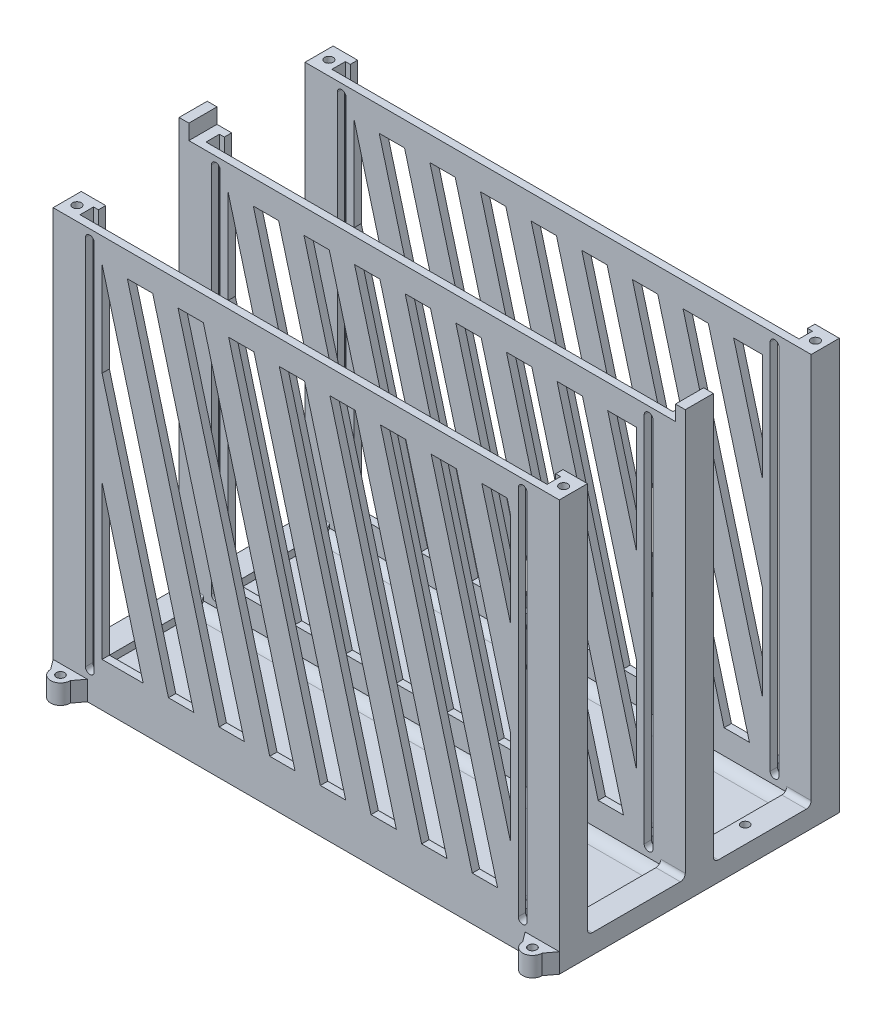
SolidWorks part; units mm, degrees
ref_plane "Front Plane" through (0, 0, 0) normal (0, 0, 1) x (1, 0, 0)
ref_plane "Top Plane" through (0, 0, 0) normal (0, 1, 0) x (1, 0, 0)
ref_plane "Right Plane" through (0, 0, 0) normal (1, 0, 0) x (0, 0, -1)
sketch "Sketch1" plane through (0, 0, 0) normal (0, 1, 0) x (1, 0, 0)
  line L0 (-95.5, 0) -> (95.5, 0) construction
  line L5 (-95.5, 2.75) -> (-93.5, 2.75)
  line L6 (-95.5, -2.75) -> (-95.5, 2.75)
  line L7 (-93.5, 2.75) -> (-93.5, 5.75)
  line L8 (-93.5, 5.75) -> (-103.5, 5.75)
  line L9 (-103.5, 5.75) -> (-103.5, -5.75)
  line L10 (-103.5, -5.75) -> (-93.5, -5.75)
  line L11 (-93.5, -5.75) -> (-93.5, -2.75)
  line L12 (-93.5, -2.75) -> (-95.5, -2.75)
  line L13 (-93.5, -2.75) -> (-93.5, -36.1204) construction
  line L14 (0, -55) -> (0, 55) construction
  line L15 (93.5, -5.75) -> (93.5, -2.75)
  line L16 (103.5, -5.75) -> (93.5, -5.75)
  line L17 (103.5, 5.75) -> (103.5, -5.75)
  line L18 (93.5, 5.75) -> (103.5, 5.75)
  line L19 (93.5, 2.75) -> (93.5, 5.75)
  line L20 (95.5, 2.75) -> (93.5, 2.75)
  line L21 (95.5, -2.75) -> (95.5, 2.75)
  line L22 (93.5, -2.75) -> (95.5, -2.75)
  line L23 (-93.5, 5.75) -> (93.5, 5.75)
  line L24 (-93.5, -5.75) -> (93.5, -5.75)
  line L25 (-93.5, -2.75) -> (93.5, -2.75)
  line L26 (93.5, 2.75) -> (-93.5, 2.75)
  line L27 (-93.5, -54.25) -> (-95.5, -54.25)
  line L28 (-95.5, -54.25) -> (-95.5, -48.75)
  line L29 (-95.5, -48.75) -> (-93.5, -48.75)
  line L30 (-93.5, -48.75) -> (-93.5, -45.75)
  line L31 (-93.5, -45.75) -> (-103.5, -45.75)
  line L32 (-103.5, -45.75) -> (-103.5, -57.25)
  line L33 (-103.5, -57.25) -> (-93.5, -57.25)
  line L34 (-93.5, -57.25) -> (-93.5, -54.25)
  line L35 (93.5, -57.25) -> (93.5, -54.25)
  line L36 (93.5, -54.25) -> (95.5, -54.25)
  line L37 (95.5, -54.25) -> (95.5, -48.75)
  line L38 (95.5, -48.75) -> (93.5, -48.75)
  line L39 (93.5, -48.75) -> (93.5, -45.75)
  line L40 (93.5, -45.75) -> (103.5, -45.75)
  line L41 (103.5, -45.75) -> (103.5, -57.25)
  line L42 (103.5, -57.25) -> (93.5, -57.25)
  line L43 (-93.5, -45.75) -> (93.5, -45.75)
  line L44 (93.5, -48.75) -> (-93.5, -48.75)
  line L45 (-93.5, -54.25) -> (93.5, -54.25)
  line L46 (-93.5, -57.25) -> (93.5, -57.25)
  line L47 (-93.5, -105.75) -> (-95.5, -105.75)
  line L48 (-95.5, -105.75) -> (-95.5, -100.25)
  line L49 (-95.5, -100.25) -> (-93.5, -100.25)
  line L50 (-93.5, -100.25) -> (-93.5, -97.25)
  line L51 (-93.5, -97.25) -> (-103.5, -97.25)
  line L52 (-103.5, -97.25) -> (-103.5, -108.75)
  line L53 (-103.5, -108.75) -> (-93.5, -108.75)
  line L54 (-93.5, -108.75) -> (-93.5, -105.75)
  line L55 (93.5, -108.75) -> (93.5, -105.75)
  line L56 (93.5, -105.75) -> (95.5, -105.75)
  line L57 (95.5, -105.75) -> (95.5, -100.25)
  line L58 (95.5, -100.25) -> (93.5, -100.25)
  line L59 (93.5, -100.25) -> (93.5, -97.25)
  line L60 (93.5, -97.25) -> (103.5, -97.25)
  line L61 (103.5, -97.25) -> (103.5, -108.75)
  line L62 (103.5, -108.75) -> (93.5, -108.75)
  line L63 (-93.5, -97.25) -> (93.5, -97.25)
  line L64 (93.5, -100.25) -> (-93.5, -100.25)
  line L65 (-93.5, -105.75) -> (93.5, -105.75)
  line L66 (-93.5, -108.75) -> (93.5, -108.75)
  line L67 (-103.5, -5.75) -> (-103.5, -45.75)
  line L68 (-93.5, -5.75) -> (-93.5, -45.75)
  line L69 (93.5, -5.75) -> (93.5, -45.75)
  line L70 (103.5, -5.75) -> (103.5, -45.75)
  line L71 (103.5, -57.25) -> (103.5, -97.25)
  line L72 (93.5, -97.25) -> (93.5, -57.25)
  line L73 (-103.5, -97.25) -> (-103.5, -57.25)
  line L74 (-93.5, -97.25) -> (-93.5, -57.25)
  line L75 (0, 5.75) -> (0, 9.75) construction
  line L76 (-96.5, 9.75) -> (96.5, 9.75) construction
  line L77 (-100.5, 9.75) -> (-103.5, 5.75)
  line L78 (-96.5, 8.05) -> (-96.5, 5.75) construction
  line L79 (-92.5, 9.75) -> (-89.5, 5.75)
  line L80 (92.5, 9.75) -> (89.5, 5.75)
  line L81 (100.5, 9.75) -> (103.5, 5.75)
  line L82 (-103.5, -51.5) -> (103.5, -51.5) construction
  line L83 (100.5, -112.75) -> (103.5, -108.75)
  line L84 (92.5, -112.75) -> (89.5, -108.75)
  line L85 (-92.5, -112.75) -> (-89.5, -108.75)
  line L86 (-100.5, -112.75) -> (-103.5, -108.75)
  circle A1 centre (96.5, 9.75) radius 1.7
  circle A2 centre (-96.5, 9.75) radius 1.7
  circle A4 centre (-96.5, 9.75) radius 4
  circle A5 centre (96.5, 9.75) radius 4
  circle A7 centre (96.5, 9.75) radius 1.7
  circle A8 centre (96.5, -112.75) radius 1.7
  circle A9 centre (96.5, -112.75) radius 4
  circle A10 centre (-96.5, -112.75) radius 1.7
  circle A12 centre (-96.5, -112.75) radius 4
  point P3 (0, 0)
  point P6 (95.5, 0)
  point P9 (-95.5, 0)
  point P61 (0, 9.75)
  dimension "D11" = 3.4
  dimension "D12" = 4
  dimension "D1" = 191
  dimension "D2" = 5.5
  dimension "D3" = 2
  dimension "D4" = 3
  dimension "D5" = 3
  dimension "D6" = 2
  dimension "D7" = 10
  dimension "D8" = 193
  dimension "D10" = 40
  dimension "D9" = 3
extrude "Boss-Extrude1" add sketch "Sketch1" against normal blind 3.2 contours L53 L54 L47 L48 L49 L50 L51 L52 | L54 L66 L55 L65 | L64 L59 L63 L50 | L34 L46 L35 L45 | L33 L34 L27 L28 L29 L30 L31 L32 | L44 L39 L43 L30 | L25 L11 L24 L15 | L26 L19 L23 L7 | L22 L15 L16 L17 L18 L19 L20 L21 | L42 L41 L40 L39 L38 L37 L36 L35 | L62 L61 L60 L59 L58 L57 L56 L55 | L11 L12 L6 L5 L7 L8 L9 L10 | L51 L74 L33 L73 | L68 L10 L67 L31 | L72 L60 L71 L42 | L70 L16 L69 L40 region at (-98.9231, 0, 0) region at (0, 0, -4.25) region at (98.9231, 0, 0) region at (0, 0, 4.25) region at (-98.5, 0, 25.75) region at (98.5, 0, 25.75) region at (0, 0, 47.25) region at (-98.9231, 0, 51.5) region at (98.9231, 0, 51.5) region at (-98.5, 0, 77.25) region at (0, 0, 55.75) region at (-98.9231, 0, 103) region at (98.5, 0, 77.25) region at (0, 0, 98.75) region at (98.9231, 0, 103) region at (0, 0, 107.25)
extrude "Boss-Extrude2" add sketch "Sketch1<4>" along normal blind 160 contours L53 L54 L47 L48 L49 L50 L51 L52 | L33 L34 L27 L28 L29 L30 L31 L32 | L11 L12 L6 L5 L7 L8 L9 L10 | L62 L61 L60 L59 L58 L57 L56 L55 | L42 L41 L40 L39 L38 L37 L36 L35 | L22 L15 L16 L17 L18 L19 L20 L21 region at (-98.9231, 0, 0) region at (98.9231, 0, 0) region at (-98.9231, 0, 51.5) region at (98.9231, 0, 51.5) region at (-98.9231, 0, 103) region at (98.9231, 0, 103)
sketch "Sketch1<4>" plane through (0, 0, 0) normal (0, 1, 0) x (1, 0, 0) same geometry as "Sketch1"
extrude "Boss-Extrude3" add sketch "Sketch1<5>" against normal blind 5 from offset 3 contours L53 L54 L47 L48 L49 L50 L51 L52 | L54 L66 L55 L65 | L47 L65 L56 L57 L58 L64 L49 L48 | L64 L59 L63 L50 | L51 L74 L33 L73 | L33 L34 L27 L28 L29 L30 L31 L32 | L34 L46 L35 L45 | L44 L39 L43 L30 | L68 L10 L67 L31 | L11 L12 L6 L5 L7 L8 L9 L10 | L25 L11 L24 L15 | L26 L19 L23 L7 | L22 L15 L16 L17 L18 L19 L20 L21 | L70 L16 L69 L40 | L42 L41 L40 L39 L38 L37 L36 L35 | L72 L60 L71 L42 | L62 L61 L60 L59 L58 L57 L56 L55 | L27 L45 L36 L37 L38 L44 L29 L28 | L20 L26 L5 L6 L12 L25 L22 L21 | L74 L63 L72 L46 | L69 L24 L68 L43 region at (-98.9231, 0, 0) region at (0, 0, 0) region at (0, 0, -4.25) region at (98.9231, 0, 0) region at (0, 0, 4.25) region at (-98.5, 0, 25.75) region at (0, 0, 25.75) region at (98.5, 0, 25.75) region at (0, 0, 47.25) region at (-98.9231, 0, 51.5) region at (98.9231, 0, 51.5) region at (0, 0, 51.5) region at (-98.5, 0, 77.25) region at (0, 0, 55.75) region at (0, 0, 77.25) region at (-98.9231, 0, 103) region at (98.5, 0, 77.25) region at (0, 0, 98.75) region at (98.9231, 0, 103) region at (0, 0, 103) region at (0, 0, 107.25) offset against normal yes
sketch "Sketch1<5>" plane through (0, 0, 0) normal (0, 1, 0) x (1, 0, 0) same geometry as "Sketch1"
fillet "Fillet1" radius 5 4 edges at (0, -3, 45.75) (0, -3, 5.75) (0, -3, 57.25) (0, -3, 97.25)
sketch "Sketch2" plane through (0, 160, 0) normal (0, 1, 0) x (1, 0, 0)
  line L0 (-95.5, 2.75) -> (-103.5, 2.75) construction
  line L1 (-103.5, 5.75) -> (-103.5, -5.75) construction
  line L2 (-95.5, -2.75) -> (-103.5, -2.75) construction
  line L3 (-99.5, 2.75) -> (-99.5, -2.75) construction
  line L4 (0, -62.975) -> (0, 62.975) construction
  line L5 (-95.5, -48.75) -> (-103.5, -48.75) construction
  line L6 (-103.5, -45.75) -> (-103.5, -57.25) construction
  line L7 (-95.5, -54.25) -> (-103.5, -54.25) construction
  line L8 (-99.5, -48.75) -> (-99.5, -54.25) construction
  line L9 (-103.5, -51.5) -> (103.5, -51.5) construction
  line L10 (103.5, -45.75) -> (103.5, -57.25) construction
  line L11 (99.5, -45.75) -> (99.5, -57.25)
  line L12 (93.5, -45.75) -> (103.5, -45.75) construction
  line L13 (103.5, -57.25) -> (93.5, -57.25) construction
  line L14 (-99.5, -45.75) -> (-99.5, -57.25)
  line L15 (-93.5, -45.75) -> (-103.5, -45.75) construction
  line L16 (-103.5, -57.25) -> (-93.5, -57.25) construction
  line L18 (-99.5, -57.25) -> (-103.5, -57.25)
  line L19 (-99.5, -57.25) -> (-99.5, -45.75)
  line L20 (-99.5, -45.75) -> (-103.5, -45.75)
  line L21 (-103.5, -57.25) -> (-103.5, -45.75)
  line L22 (99.5, -45.75) -> (103.5, -45.75)
  line L23 (99.5, -45.75) -> (99.5, -57.25)
  line L24 (99.5, -57.25) -> (103.5, -57.25)
  line L25 (103.5, -45.75) -> (103.5, -57.25)
  circle A0 centre (-99.5, 0) radius 1.75
  circle A1 centre (99.5, 0) radius 1.75
  circle A2 centre (-99.5, -51.5) radius 1.75 construction
  circle A3 centre (99.5, -51.5) radius 1.75 construction
  circle A4 centre (-99.5, -103) radius 1.75
  circle A5 centre (99.5, -103) radius 1.75
  dimension "D1" = 3.5
  dimension "D2" = 3
extrude "Cut-Extrude1" cut sketch "Sketch2" against normal blind 5 contours A0 | A1 | A5 | A4 region at (-99.5, 160, 0) region at (99.5, 160, 0) region at (-99.5, 160, 103) region at (99.5, 160, 103)
fillet "Fillet2" radius 2 8 edges at (-98.5, 0, 5.75) (-98.5, 0, 57.25) (-98.5, 0, 45.75) (-98.5, 0, 97.25) (98.5, 0, 45.75) (98.5, 0, 5.75) (98.5, 0, 57.25) (98.5, 0, 97.25)
sketch "Sketch3" plane through (0, 0, 108.75) normal (0, 0, 1) x (1, 0, 0)
  line L0 (-93.5, 160) -> (93.5, 160)
  line L1 (-93.5, 160) -> (93.5, 0) construction
  line L2 (-93.5, 160) -> (93.5, 160)
  line L3 (-93.5, 160) -> (-93.5, 0)
  line L4 (-93.5, 0) -> (93.5, 0)
  line L5 (93.5, 160) -> (93.5, 0)
  line L6 (-83.5, 150) -> (-45.9871, 10)
  line L7 (-83.5, 10) -> (83.5, 10)
  line L8 (-83.5, 10) -> (-83.5, 150)
  line L9 (-83.5, 150) -> (83.5, 150)
  line L10 (83.5, 10) -> (83.5, 150)
  line L11 (0, 150) -> (0, 10) construction
  line L12 (-83.5, 80) -> (83.5, 80) construction
  line L13 (-73.1472, 150) -> (-35.6344, 10)
  line L14 (-52.4417, 150) -> (-14.9288, 10)
  line L15 (-62.7945, 150) -> (-25.2816, 10)
  line L16 (-31.7362, 150) -> (5.7767, 10)
  line L17 (-42.089, 150) -> (-4.5761, 10)
  line L18 (-11.0307, 150) -> (26.4822, 10)
  line L19 (-21.3834, 150) -> (16.1295, 10)
  line L20 (9.6749, 150) -> (47.1877, 10)
  line L21 (-0.6779, 150) -> (36.835, 10)
  line L22 (30.3804, 150) -> (67.8933, 10)
  line L23 (20.0276, 150) -> (57.5405, 10)
  line L24 (51.0859, 150) -> (88.5988, 10)
  line L25 (40.7331, 150) -> (78.246, 10)
  line L26 (71.7914, 150) -> (83.5, 106.303)
  line L27 (61.4387, 150) -> (83.5, 67.666)
  line L28 (-88.5, 160) -> (-88.5, 156) construction
  line L29 (82.1442, 150) -> (83.5, 144.94)
  line L30 (-56.3399, 10) -> (-83.5, 111.363)
  line L31 (-83.5, 72.7259) -> (-66.6926, 10)
  line L32 (98.412, 127.9247) -> (99.5066, 123.8397) [skipped]
  line L33 (-90.3, 156) -> (-90.3, 4)
  line L34 (-86.7, 4) -> (-86.7, 156)
  line L35 (86.7, 4) -> (86.7, 156)
  line L36 (90.3, 156) -> (90.3, 4)
  circle A1 centre (-88.5, 156) radius 1.8
  circle A2 centre (-88.5, 4) radius 1.8
  circle A3 centre (88.5, 4) radius 1.8
  circle A4 centre (88.5, 156) radius 1.8
  point P6 (0, 80)
  point P40 (-88.5, 160)
  point P53 (-88.5, 0)
  line M38 (93.5, 160) -> (93.5, 0)
  line M39 (93.5, 0) -> (-93.5, 0)
  line M40 (-93.5, 0) -> (-93.5, 160)
  dimension "D11" = 3.6
  dimension "D1" = 10
  dimension "D2" = 10
  dimension "D3" = 15
  dimension "D4" = 10
  dimension "D6" = 10
  dimension "D7" = 10
  dimension "D8" = 10
  dimension "D9" = 5
  dimension "D10" = 4
  dimension "D5" = 9
extrude "Boss-Extrude4" add sketch "Sketch3" against normal up to vertex (3 mm away) contours L0 L10 L7 L8 L9 M40 M39 M38 | L8 L31 L7 L30 | L13 L9 L6 L7 | L9 L15 L7 L14 | L9 L17 L7 L16 | L9 L19 L7 L18 | L9 L21 L7 L20 | L9 L23 L7 L22 | L9 L25 L7 L24 | L9 L27 L10 L26 | L9 L29 L10 region at (0, 157.5389, 108.75) region at (-59.5672, 80, 108.75) region at (-72.305, 51.7804, 108.75) region at (-38.8617, 80, 108.75) region at (-18.1561, 80, 108.75) region at (2.5494, 80, 108.75) region at (23.2549, 80, 108.75) region at (43.9604, 80, 108.75) region at (63.9549, 82.2044, 108.75) region at (74.793, 117.5052, 108.75) region at (83.0481, 148.3133, 108.75) up to point (-95.5, -3, 105.75)
sketch "Sketch4" plane through (0, 0, 57.25) normal (0, 0, 1) x (1, 0, 0)
  line L0 (-93.5, 160) -> (93.5, 0) construction
  line L1 (-93.5, 160) -> (93.5, 160)
  line L2 (-93.5, 160) -> (-93.5, 0)
  line L3 (-93.5, 0) -> (93.5, 0)
  line L4 (93.5, 160) -> (93.5, 0)
  line L5 (-83.5, 150) -> (-45.9871, 10)
  line L6 (-83.5, 10) -> (83.5, 10)
  line L7 (-83.5, 10) -> (-83.5, 150)
  line L8 (-83.5, 150) -> (83.5, 150)
  line L9 (83.5, 10) -> (83.5, 150)
  line L10 (0, 150) -> (0, 10) construction
  line L11 (-83.5, 80) -> (83.5, 80) construction
  line L12 (-73.1472, 150) -> (-35.6344, 10)
  line L13 (-52.4417, 150) -> (-14.9288, 10)
  line L14 (-62.7945, 150) -> (-25.2816, 10)
  line L15 (-31.7362, 150) -> (5.7767, 10)
  line L16 (-42.089, 150) -> (-4.5761, 10)
  line L17 (-11.0307, 150) -> (26.4822, 10)
  line L18 (-21.3834, 150) -> (16.1295, 10)
  line L19 (9.6749, 150) -> (47.1877, 10)
  line L20 (-0.6779, 150) -> (36.835, 10)
  line L21 (30.3804, 150) -> (67.8933, 10)
  line L22 (20.0276, 150) -> (57.5405, 10)
  line L23 (51.0859, 150) -> (88.5988, 10)
  line L24 (40.7331, 150) -> (78.246, 10)
  line L25 (71.7914, 150) -> (83.5, 106.303)
  line L26 (61.4387, 150) -> (83.5, 67.666)
  line L27 (-56.3399, 10) -> (-83.5, 111.363)
  line L28 (-66.6926, 10) -> (-83.5, 72.7259)
  line L29 (99.997, 122.0096) -> (101, 118.2662) [skipped]
  line L30 (89.6442, 122.0096) -> (91, 116.9497) [skipped]
  point P5 (0, 80)
  line M15 (93.5, 160) -> (93.5, 2)
  dimension "D1" = 10
  dimension "D2" = 10
  dimension "D3" = 15
  dimension "D4" = 10
  dimension "D6" = 10
  dimension "D7" = 10
  dimension "D8" = 10
  dimension "D5" = 9
extrude "Boss-Extrude5" add sketch "Sketch4" against normal blind 3 contours L4 L1 L2 L3 L9 L6 L7 L8 M15 | L12 L8 L5 L6 | L28 L6 L27 L7 | L8 L14 L6 L13 | L8 L16 L6 L15 | L8 L18 L6 L17 | L8 L20 L6 L19 | L8 L22 L6 L21 | L8 L24 L6 L23 | L8 L26 L9 L25 region at (0, 157.5389, 57.25) region at (-59.5672, 80, 57.25) region at (-72.305, 51.7804, 57.25) region at (-38.8617, 80, 57.25) region at (-18.1561, 80, 57.25) region at (2.5494, 80, 57.25) region at (23.2549, 80, 57.25) region at (43.9604, 80, 57.25) region at (63.9549, 82.2044, 57.25) region at (74.793, 117.5052, 57.25)
pattern_linear "LPattern1" count 2 spacing 51.5 along (0, 0, -1) of "Boss-Extrude5"
sketch "Sketch5" plane through (0, 0, 0) normal (0, 1, 0) x (1, 0, 0)
  line L0 (-103.5, -51.5) -> (103.5, -51.5) construction
  line L1 (-103.5, -45.75) -> (-103.5, -57.25) construction
  line L2 (103.5, -45.75) -> (103.5, -57.25) construction
  line L3 (0, 5.75) -> (0, -108.75) construction
  line L4 (-93.5, 5.75) -> (93.5, 5.75) construction
  line L5 (103.5, -108.75) -> (-103.5, -108.75) construction
  line L9 (-96.5, -25.75) -> (96.5, -25.75) construction
  line L10 (-103.5, -25.75) -> (-93.5, -25.75) construction
  line L11 (-103.5, -7.75) -> (-103.5, -43.75) construction
  line L12 (-93.5, -41.1674) -> (-93.5, -10.3326) construction
  circle A0 centre (96.5, -25.75) radius 1.7
  circle A1 centre (-96.5, -25.75) radius 1.7
  circle A2 centre (-96.5, -77.25) radius 1.7
  circle A3 centre (96.5, -77.25) radius 1.7
  point P21 (0, -25.75)
  point P27 (-96.5, -25.75)
  dimension "D2" = 3.4
  dimension "D1" = 193
extrude "BASEPLATE HOLES" cut sketch "Sketch5" against normal blind 10 contours A1 | A0 region at (96.5, 0, 25.75) region at (-96.5, 0, 25.75)
extrude "Boss-Extrude6" add sketch "Sketch2<4>" along normal blind 6.2 contours L25 L22 L11 L24 | L21 L18 L14 L20 region at (101.5, 160, 51.5) region at (-101.5, 160, 51.5)
sketch "Sketch2<4>" plane through (0, 160, 0) normal (0, 1, 0) x (1, 0, 0) same geometry as "Sketch2"
extrude "Cut-Extrude3" cut sketch "Sketch3<3>" against normal through all contours L33 A2 L34 A1 | A2 | A1 | A4 | L36 A4 L35 A3 | A3 region at (88.5, 80, 108.75) region at (88.5, 4, 108.75) region at (88.5, 156, 108.75) region at (-88.5, 80, 108.75) region at (-88.5, 156, 108.75) region at (-88.5, 4, 108.75)
sketch "Sketch3<3>" plane through (0, 0, 108.75) normal (0, 0, 1) x (1, 0, 0) same geometry as "Sketch3"
extrude "BASEPLATEHOLES2" add sketch "Sketch1<6>" against normal up to surface (8 mm away) contours A9 L62 L66 L84 | A9 A8 | A9 L83 L62 | L86 A12 L53 | A12 A10 | L53 A12 L85 L66 region at (-100.8108, 0, 109.9232) region at (-92.1892, 0, 109.9232) region at (-93.7516, 0, 110.0016) region at (100.8108, 0, 109.9232) region at (92.1892, 0, 109.9232) region at (99.2484, 0, 110.0016) up to face at (96.5, -8, 27.45)
sketch "Sketch1<6>" plane through (0, 0, 0) normal (0, 1, 0) x (1, 0, 0) same geometry as "Sketch1"
